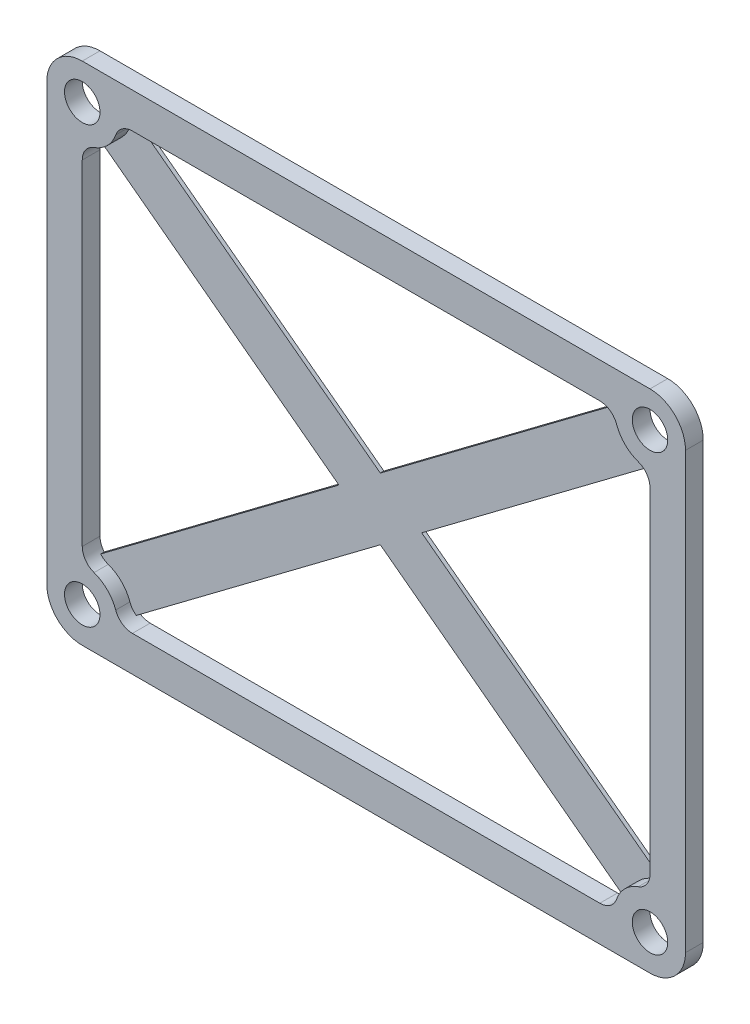
SolidWorks part; units mm, degrees
ref_plane "Front Plane" through (0, 0, 0) normal (0, 0, 1) x (1, 0, 0)
ref_plane "Top Plane" through (0, 0, 0) normal (0, 1, 0) x (1, 0, 0)
ref_plane "Right Plane" through (0, 0, 0) normal (1, 0, 0) x (0, 0, -1)
sketch "Sketch1" plane through (0, 0, 0) normal (0, 0, 1) x (1, 0, 0)
  line L0 (-101.6, -114.3) -> (101.6, -114.3) construction
  line L1 (-101.6, 101.6) -> (101.6, 101.6) construction
  line L2 (-101.6, 101.6) -> (-101.6, -41.402) construction
  line L3 (-101.6, -101.6) -> (101.6, -101.6) construction
  line L4 (101.6, 101.6) -> (101.6, -41.402) construction
  line L5 (-101.6, 101.6) -> (101.6, -101.6) construction
  line L6 (-101.6, -101.6) -> (101.6, 101.6) construction
  line L7 (114.3, -101.6) -> (114.3, 101.6) construction
  line L8 (-114.3, -101.6) -> (-114.3, 101.6) construction
  line L9 (-101.6, 114.3) -> (101.6, 114.3)
  line L10 (-101.6, 88.9) -> (-101.6, -41.402)
  line L11 (-88.9, -101.6) -> (88.9, -101.6) construction
  line L12 (101.6, -88.9) -> (101.6, -60.452) construction
  line L13 (88.9, 101.6) -> (-88.9, 101.6)
  line L14 (-101.6, -60.452) -> (-101.6, -101.6) construction
  line L15 (-101.6, -60.452) -> (-101.6, -88.9) construction
  line L16 (0, -55) -> (0, 55) construction
  line L17 (-88.9, -54.102) -> (-88.9, -101.6) construction
  line L18 (101.6, -41.402) -> (101.6, 88.9)
  line L19 (88.9, -101.6) -> (88.9, -54.102) construction
  line L20 (101.6, -60.452) -> (101.6, -101.6) construction
  line L21 (-114.3, -66.802) -> (114.3, -66.802)
  line L22 (-88.9, -54.102) -> (88.9, -54.102)
  line L23 (-114.3, 101.6) -> (-114.3, -66.802)
  line L24 (114.3, -66.802) -> (114.3, 101.6)
  arc A0 (-101.6, 88.9) -> (-88.9, 101.6) centre (-101.6, 101.6) ccw
  circle A1 centre (-101.6, 101.6) radius 6.35
  circle A2 centre (101.6, 101.6) radius 6.35
  arc A3 (88.9, 101.6) -> (101.6, 88.9) centre (101.6, 101.6) ccw
  circle A4 centre (101.6, -101.6) radius 6.35 construction
  arc A5 (101.6, -88.9) -> (88.9, -101.6) centre (101.6, -101.6) ccw construction
  circle A6 centre (-101.6, -101.6) radius 6.35 construction
  arc A7 (-88.9, -101.6) -> (-101.6, -88.9) centre (-101.6, -101.6) ccw construction
  arc A8 (-101.6, 114.3) -> (-114.3, 101.6) centre (-101.6, 101.6) ccw
  arc A9 (114.3, 101.6) -> (101.6, 114.3) centre (101.6, 101.6) ccw
  arc A10 (101.6, -114.3) -> (114.3, -101.6) centre (101.6, -101.6) ccw construction
  arc A11 (-114.3, -101.6) -> (-101.6, -114.3) centre (-101.6, -101.6) ccw construction
  circle A12 centre (-101.6, -54.102) radius 6.35
  arc A13 (-88.9, -54.102) -> (-101.6, -41.402) centre (-101.6, -54.102) ccw
  circle A14 centre (101.6, -54.102) radius 6.35
  arc A15 (88.9, -54.102) -> (101.6, -41.402) centre (101.6, -54.102) cw
  point P0 (0, 0)
  dimension "D3" = 25.4
  dimension "D4" = 12.7
  dimension "D7" = 12.7
  dimension "D9" = 25.4
  dimension "D1" = 203.2
  dimension "D2" = 203.2
  dimension "D8" = 47.498
  dimension "D10" = 12.7
  dimension "D5" = 2
  dimension "D6" = 2
extrude "Outline" add sketch "Sketch1" along normal blind 6.35
fillet "Fillet2" radius 12.7 2 edges at (114.3, -66.802, 3.175) (-114.3, -66.802, 3.175)
sketch "Sketch2" plane through (0, 0, 0) normal (0, 0, -1) x (-1, 0, 0)
  line L11 (-101.6, 88.9) -> (-14.8091, 23.749)
  line L12 (-88.9, 101.6) -> (0, 34.8657)
  line L13 (101.6, 88.9) -> (14.8091, 23.749)
  line L14 (-101.6, -41.402) -> (-14.8091, 23.749)
  line L15 (0, 12.6323) -> (88.9, -54.102)
  line L16 (14.8091, 23.749) -> (101.6, -41.402)
  line L17 (0, 34.8657) -> (88.9, 101.6)
  line L18 (0, 12.6323) -> (-88.9, -54.102)
  arc A0 (88.9, 101.6) -> (101.6, 88.9) centre (101.6, 101.6) ccw construction
  arc A1 (101.6, -41.402) -> (88.9, -54.102) centre (101.6, -54.102) ccw construction
  arc A8 (-88.9, -54.102) -> (-101.6, -41.402) centre (-101.6, -54.102) ccw construction
  arc A9 (-101.6, 88.9) -> (-88.9, 101.6) centre (-101.6, 101.6) ccw construction
  arc A10 (88.9, 101.6) -> (101.6, 88.9) centre (101.6, 101.6) ccw
  arc A11 (101.6, -41.402) -> (88.9, -54.102) centre (101.6, -54.102) ccw
  arc A12 (-88.9, -54.102) -> (-101.6, -41.402) centre (-101.6, -54.102) ccw
  arc A13 (-101.6, 88.9) -> (-88.9, 101.6) centre (-101.6, 101.6) ccw
extrude "Boss-Extrude1" add sketch "Sketch2" against normal blind 1.27
fillet "Fillet1" radius 6.35 8 edges at (101.6, 88.9, 3.81) (88.9, 101.6, 3.81) (-101.6, 88.9, 3.81) (-88.9, 101.6, 3.81) (-101.6, -41.402, 3.81) (101.6, -41.402, 3.81) (-88.9, -54.102, 3.81) (88.9, -54.102, 3.81) tangent propagation no
